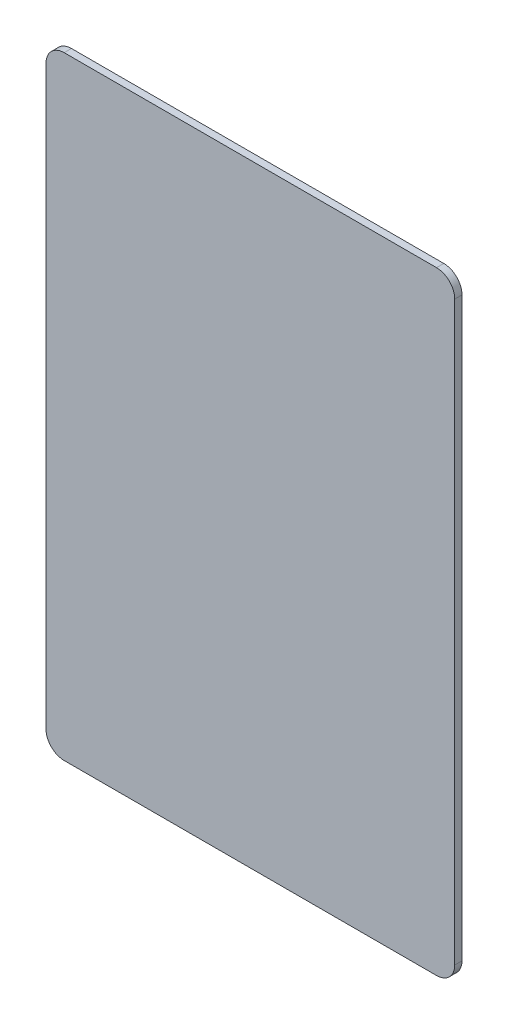
SolidWorks part; units mm, degrees
material "Plastique personnalisé"
ref_plane "Plan de face" through (0, 0, 0) normal (0, 0, 1) x (1, 0, 0)
ref_plane "Plan de dessus" through (0, 0, 0) normal (0, 1, 0) x (1, 0, 0)
ref_plane "Plan de droite" through (0, 0, 0) normal (1, 0, 0) x (0, 0, -1)
sketch "Esquisse1" plane through (0, 0, 0) normal (0, 0, 1) x (1, 0, 0)
  line L1 (4, 0) -> (86, 0)
  line L2 (0, -4) -> (0, -131)
  line L3 (4, -135) -> (86, -135)
  line L4 (90, -4) -> (90, -131)
  arc A0 (0, -131) -> (4, -135) centre (4, -131) ccw
  arc A1 (86, -135) -> (90, -131) centre (86, -131) ccw
  arc A2 (86, 0) -> (90, -4) centre (86, -4) cw
  arc A3 (4, 0) -> (0, -4) centre (4, -4) ccw
  point P9 (90, -135)
  point P12 (90, 0)
  point P15 (0, 0)
  dimension "D3" = 4
  dimension "D1" = 90
  dimension "D2" = 135
extrude "Boss.-Extru.1" add sketch "Esquisse1" along normal blind 1.6
sketch "Esquisse2" plane through (0, 0, 1.6) normal (0, 0, 1) x (1, 0, 0)
  line L0 (0, 0) -> (45, 0) construction
  line L1 (86, 0) -> (4, 0) construction
  line L2 (45, 0) -> (45, 1.7863) construction
ref_axis "Axe1" through (45, 0, 1.6) along (0, 1, 0)
